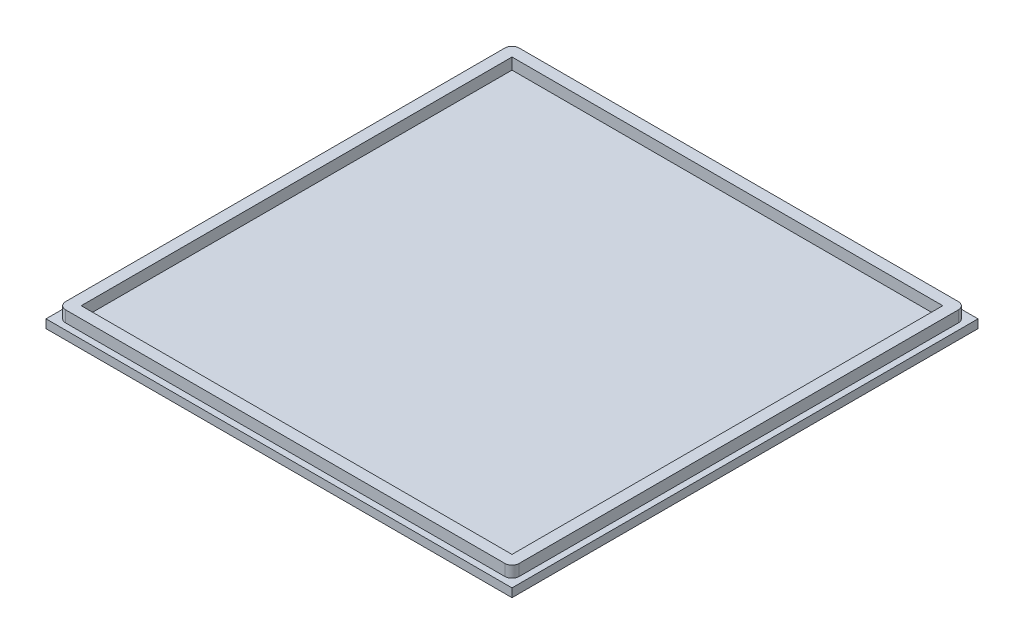
SolidWorks part; units mm, degrees
ref_plane "Front Plane" through (0, 0, 0) normal (0, 0, 1) x (1, 0, 0)
ref_plane "Top Plane" through (0, 0, 0) normal (0, 1, 0) x (1, 0, 0)
ref_plane "Right Plane" through (0, 0, 0) normal (1, 0, 0) x (0, 0, -1)
sketch "Sketch1" plane through (0, 0, 0) normal (0, 1, 0) x (1, 0, 0)
  line L2 (-82, 82) -> (82, 82)
  line L3 (-82, 82) -> (-82, -82)
  line L4 (-82, -82) -> (82, -82)
  line L5 (82, 82) -> (82, -82)
  line L6 (-82, 82) -> (82, -82) construction
  line L7 (-82, -82) -> (82, 82) construction
  point P1 (0, 0)
  dimension "D1" = 164
  dimension "D2" = 164
extrude "Boss-Extrude1" add sketch "Sketch1" along normal blind 3
sketch "Sketch2" plane through (0, 3, 0) normal (0, 1, 0) x (1, 0, 0)
  line L0 (79.8, -82) -> (82, -82) construction
  line L1 (-82, -82) -> (-79.8, -82) construction
  line L2 (-82, -82) -> (-82, -79.8) construction
  line L3 (-82, -79.8) -> (-79.8, -79.8) construction
  line L4 (-79.8, -82) -> (-79.8, -79.8) construction
  line L5 (79.8, -82) -> (79.8, -79.8) construction
  line L6 (79.8, -79.8) -> (82, -79.8) construction
  line L7 (82, -82) -> (82, -79.8) construction
  line L12 (79.8, 79.8) -> (82, 79.8) construction
  line L13 (79.8, 79.8) -> (79.8, 82) construction
  line L14 (79.8, 82) -> (82, 82) construction
  line L15 (82, 79.8) -> (82, 82) construction
  line L16 (-82, 79.8) -> (-79.8, 79.8) construction
  line L17 (-82, 79.8) -> (-82, 82) construction
  line L18 (-82, 82) -> (-79.8, 82) construction
  line L19 (-79.8, 79.8) -> (-79.8, 82) construction
  line L20 (-76.4694, -74.5035) -> (-71.4694, -74.5035) construction
  line L21 (-77.3, -79.8) -> (77.3, -79.8)
  line L22 (-79.8, -77.3) -> (-79.8, 77.3)
  line L23 (-77.3, 79.8) -> (77.3, 79.8)
  line L24 (79.8, -77.3) -> (79.8, 77.3)
  line L25 (-71.4694, -74.5035) -> (-71.4694, -79.5035) construction
  line L26 (-71.4694, -79.5035) -> (-76.4694, -74.5035) construction
  arc A0 (-79.8, -77.3) -> (-77.3, -79.8) centre (-77.3, -77.3) ccw
  arc A1 (79.8, 77.3) -> (77.3, 79.8) centre (77.3, 77.3) ccw
  arc A2 (77.3, -79.8) -> (79.8, -77.3) centre (77.3, -77.3) ccw
  arc A3 (-77.3, 79.8) -> (-79.8, 77.3) centre (-77.3, 77.3) ccw
  point P11 (-75.299, 75.4914)
  dimension "D1" = 2.2
  dimension "D2" = 2.2
  dimension "D3" = 2.2
extrude "Extrude-Thin1" add sketch "Sketch2" along normal blind 4 thin thin type one direction reverse wall 4
